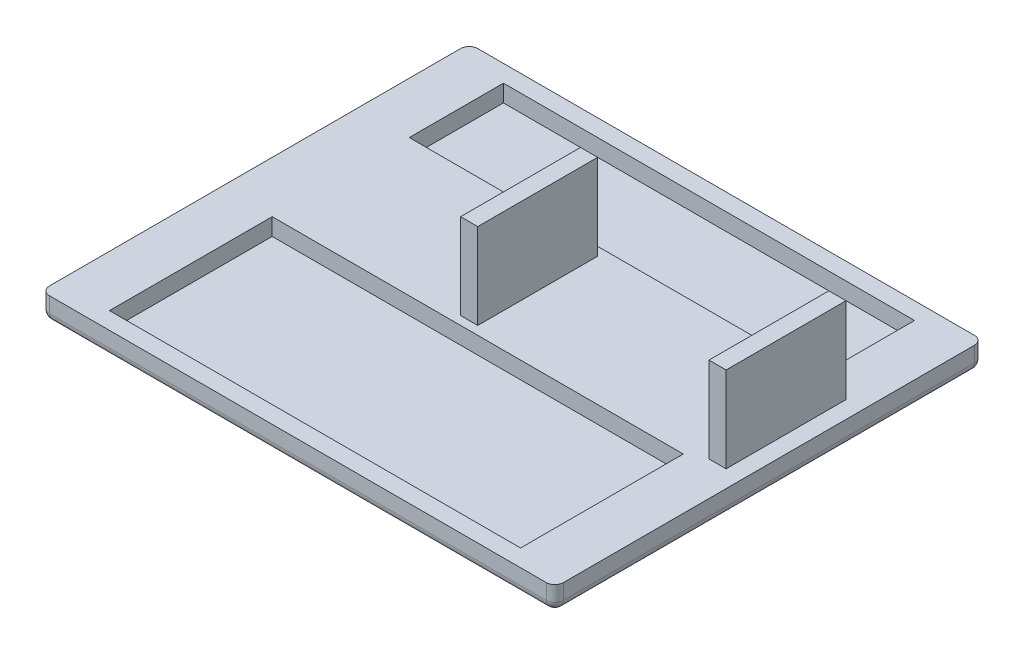
SolidWorks part; units mm, degrees
ref_plane "Front Plane" through (0, 0, 0) normal (0, 0, 1) x (1, 0, 0)
ref_plane "Top Plane" through (0, 0, 0) normal (0, 1, 0) x (1, 0, 0)
ref_plane "Right Plane" through (0, 0, 0) normal (1, 0, 0) x (0, 0, -1)
sketch "Sketch1" plane through (0, 0, 0) normal (0, 1, 0) x (1, 0, 0)
  line L1 (-150, -125) -> (150, -125)
  line L2 (-150, -125) -> (-150, 125)
  line L3 (-150, 125) -> (150, 125)
  line L4 (150, -125) -> (150, 125)
  line L5 (-150, -125) -> (150, 125) construction
  line L6 (-150, 125) -> (150, -125) construction
  point P0 (0, 0)
  dimension "D1" = 300
  dimension "D2" = 250
extrude "Base" add sketch "Sketch1" along normal blind 14
sketch "Sketch3" plane through (0, 14, 0) normal (0, 1, 0) x (1, 0, 0)
  line L0 (-120, 115) -> (-120, -115)
  line L1 (-120, 115) -> (120, 115)
  line L3 (-120, -115) -> (120, -115)
  line L5 (120, 115) -> (120, -115)
  line L6 (150, 125) -> (-150, 125) construction
  line L7 (-150, 125) -> (-150, -125) construction
  line L8 (150, -125) -> (150, 125) construction
  line L12 (-150, -125) -> (150, -125) construction
  point P0 (0, 0)
  dimension "D3" = 10
  dimension "D5" = 10
  dimension "D1" = 30
  dimension "D2" = 30
extrude "Cut-Extrude1" cut sketch "Sketch3" against normal blind 10
fillet "Fillet1" radius 5 4 edges at (0, 0, -125) (-150, 0, 0) (0, 0, 125) (150, 0, 0)
fillet "Fillet2" radius 5 8 edges at (-148.5355, 1.4645, 123.5355) (-150, 9.5, 125) (148.5355, 1.4645, -123.5355) (148.5355, 1.4645, 123.5355) (-148.5355, 1.4645, -123.5355) (150, 9.5, -125) (150, 9.5, 125) (-150, 9.5, -125)
sketch "Sketch4" plane through (0, 4, 0) normal (0, 1, 0) x (1, 0, 0)
  line L0 (-120, 115) -> (-120, -115) construction
  line L1 (-120, 60) -> (120, 60)
  line L2 (-120, 60) -> (-120, -20)
  line L3 (-120, -20) -> (120, -20)
  line L4 (120, 60) -> (120, -20)
  line L5 (120, -115) -> (120, 115) construction
  line L7 (145, 125) -> (-145, 125) construction
  dimension "D1" = 80
  dimension "D2" = 65
extrude "DIN Base" add sketch "Sketch4" along normal blind 10
sketch "Sketch5" plane through (0, 14, 0) normal (0, 1, 0) x (1, 0, 0)
  line L0 (150, -120) -> (150, 120) construction
  line L1 (130, 55) -> (140, 55)
  line L2 (130, 55) -> (130, -15)
  line L3 (130, -15) -> (140, -15)
  line L4 (140, 55) -> (140, -15)
  line L5 (-15, 55) -> (-5, 55)
  line L6 (-15, 55) -> (-15, -15)
  line L7 (-15, -15) -> (-5, -15)
  line L8 (-5, 55) -> (-5, -15)
  line L9 (0, 60) -> (0, -20) construction
  line L10 (120, 60) -> (-120, 60) construction
  line L11 (-120, -20) -> (120, -20) construction
  line L12 (-5, 20) -> (0, 20) construction
  dimension "D3" = 10
  dimension "D1" = 135
  dimension "D4" = 70
extrude "DIN Stand" add sketch "Sketch5" along normal blind 50
equation "\"Width\"= 300"
equation "\"D1@Sketch1\"=\"Width\""
equation "\"Depth\"= 250"
equation "\"D2@Sketch1\"=\"Depth\""
equation "\"height\"= 14"
equation "\"D1@Base\"=\"height\""
equation "\"r1\"=5"
equation "\"D1@Fillet2\"=\"r1\""
equation "\"D1@Fillet1\"=\"r1\""
equation "\"cut1\"= 10"
equation "\"D1@Cut-Extrude1\"=\"cut1\""
equation "\"border1\"=10"
equation "\"D3@Sketch3\"=\"border1\""
equation "\"D5@Sketch3\"=\"border1\""
equation "\"rail_mount_width\"=130"
equation "\"border2\"= 30"
equation "\"D1@Sketch3\"=\"border2\""
equation "\"D2@Sketch3\"=\"border2\""
equation "\"mounting_w\"=80"
equation "\"D1@Sketch4\"=\"mounting_w\""
equation "\"mounting_offset\"=65"
equation "\"D2@Sketch4\"=\"mounting_offset\""
equation "\"D1@DIN Base\" = \"border1\""
equation "\"Stand1_dist\"= 135"
equation "\"D1@Sketch5\"=\"Stand1_dist\""
equation "\"D2@Sketch5\"=\"border1\""
equation "\"D3@Sketch5\"=\"border1\""
equation "\"din_stand_height\"=50"
equation "\"D1@DIN Stand\"=\"din_stand_height\""
